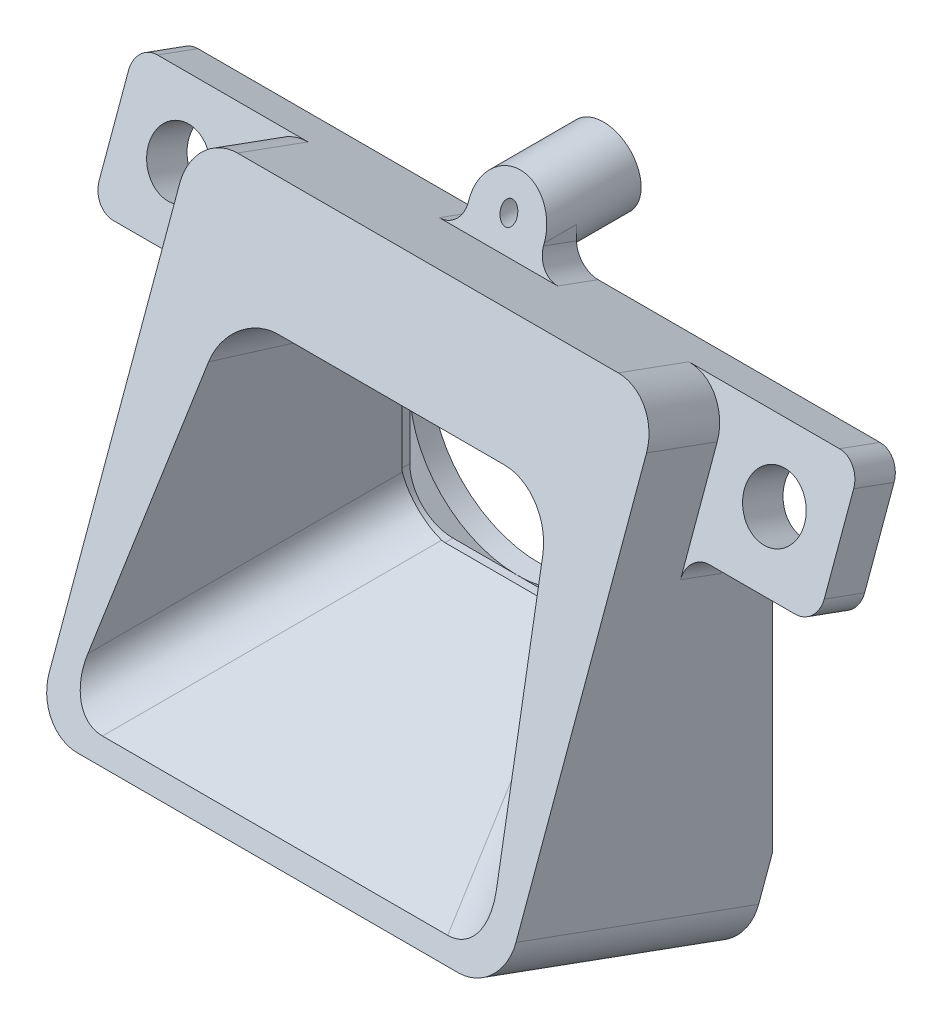
SolidWorks part; units mm, degrees
ref_plane "Front" through (0, 0, 0) normal (0, 0, 1) x (1, 0, 0)
ref_plane "Top" through (0, 0, 0) normal (0, 1, 0) x (1, 0, 0)
ref_plane "Right" through (0, 0, 0) normal (1, 0, 0) x (0, 0, -1)
sketch "Sketch1" plane through (0, 0, 0) normal (0, 0, 1) x (1, 0, 0)
  line L1 (0, 0) -> (40, 0)
  line L2 (0, 0) -> (0, 21.55)
  line L3 (0, 21.55) -> (40, 21.55)
  line L4 (40, 0) -> (40, 21.55)
  dimension "D1" = 40
  dimension "D2" = 21.55
extrude "Boss-Extrude1" add sketch "Sketch1" along normal blind 12.6
sketch "Sketch2" plane through (0, 0, 12.6) normal (0, 0, 1) x (1, 0, 0)
  line L0 (20, 21.55) -> (20, 0) construction
  line L1 (40, 21.55) -> (0, 21.55) construction
  line L2 (0, 0) -> (40, 0) construction
  circle A0 centre (20, 10.775) radius 5
  dimension "D1" = 10
extrude "Cut-Extrude1" cut sketch "Sketch2" against normal through all
sketch "Sketch3" plane through (0, 0, 12.6) normal (0, 0, 1) x (1, 0, 0)
  line L1 (15, 5.775) -> (25, 5.775)
  line L2 (15, 5.775) -> (15, 15.775)
  line L3 (15, 15.775) -> (25, 15.775)
  line L4 (25, 5.775) -> (25, 15.775)
  line L5 (15, 5.775) -> (25, 15.775) construction
  line L6 (15, 15.775) -> (25, 5.775) construction
  circle A0 centre (20, 10.775) radius 5 construction
  point P0 (20, 10.775)
extrude "Cut-Extrude2" cut sketch "Sketch3" against normal offset from surface (11.6 mm away) 1 up to face at (25, 10.775, 0)
chamfer "Chamfer1" distance 5 angle 66 3 edges at (25, 10.775, 12.6) (15, 10.775, 12.6) (20, 5.775, 12.6) first distance on face at (20, 10.775, 12.6)
sketch "Sketch4" plane through (0, 0, 0) normal (-1, 0, 0) x (0, 0, 1)
  line L0 (12.6, 0) -> (5.1642, 20.4296)
  line L1 (5.1642, 20.4296) -> (0, 18.55)
  line L4 (12.6, 0) -> (12.6, 21.55)
  line L5 (0, 21.55) -> (0, 0) construction
  line L6 (0, 18.55) -> (0, 21.55)
  line L7 (0, 21.55) -> (12.6, 21.55)
  dimension "D1" = 20
  dimension "D2" = 3
extrude "Cut-Extrude3" cut sketch "Sketch4" against normal through all
sketch "Sketch5" plane through (0, 0, 0) normal (-1, 0, 0) x (0, 0, 1)
  line L0 (12.6, 0) -> (0, -4.586)
  line L1 (0, -4.586) -> (0, 0)
  line L2 (12.6, 0) -> (0, 0) construction
  line L3 (0, 0) -> (12.6, 0)
  line L4 (0, 18.55) -> (5.1642, 20.4296) construction
  line L5 (0, 18.55) -> (0, 0) construction
extrude "Boss-Extrude2" add sketch "Sketch5" against normal up to surface (40 mm away) up to face at (40, 9.7449, 4.4411)
sketch "Sketch6" plane through (0, 0, -3) normal (0, 0, 1) x (1, 0, 0)
  circle A0 centre (20, 20.275) radius 1.75
  circle A1 centre (20, 1.275) radius 1.75
  dimension "D1" = 3.5
extrude "Boss-Extrude3" add sketch "Sketch6" along normal up to surface (3 mm away) up to face at (20, 6.982, 0)
sketch "Sketch7" plane through (40, 0, 0) normal (1, 0, 0) x (0, 0, -1)
  line L0 (0, -4.586) -> (0, -0.475)
  line L2 (0, -0.475) -> (-1.3213, -4.1051)
  line L3 (-12.6, 0) -> (0, -4.586) construction
  line L4 (-1.3213, -4.1051) -> (0, -4.586)
  line L5 (0, -0.475) -> (0, 3.025) construction
  line L6 (0, -0.475) -> (0, 3.025) construction
extrude "Cut-Extrude4" cut sketch "Sketch7" against normal through all
sketch "Sketch8" plane through (0, 4.0496, 11.1261) normal (0, 0.342, 0.9397) x (1, 0, 0)
  line L0 (0, -4.3095) -> (40, -4.3095) construction
  line L1 (0, 17.4313) -> (9.1499, 17.4313)
  line L2 (0, 17.4313) -> (0, -4.3095)
  line L3 (0, -4.3095) -> (9.1499, -4.3095)
  line L4 (9.1499, 17.4313) -> (9.1499, -4.3095)
  line L5 (20, -4.3095) -> (20, 17.4313) construction
  line L6 (40, 17.4313) -> (0, 17.4313) construction
  line L7 (40, -4.3095) -> (30.8501, -4.3095)
  line L8 (30.8501, 17.4313) -> (30.8501, -4.3095)
  line L9 (40, 17.4313) -> (30.8501, 17.4313)
  line L10 (40, 17.4313) -> (40, -4.3095)
  dimension "D1" = 1
extrude "Cut-Extrude5" cut sketch "Sketch8" against normal through all
sketch "Sketch11" plane through (9.1499, 0, 0) normal (-1, 0, 0) x (0, 0, 1)
  line L0 (0, 18.55) -> (1.8794, 19.234)
  line L1 (0, 18.55) -> (2.0521, 12.9118)
  line L2 (1.8794, 19.234) -> (3.9315, 13.5959)
  line L3 (2.0521, 12.9118) -> (3.9315, 13.5959)
  line L4 (0, 18.55) -> (5.1642, 20.4296) construction
  dimension "D1" = 2
  dimension "D2" = 6
extrude "Boss-Extrude4" add sketch "Sketch11" along normal blind 6
ref_plane "Plane1" through (20, 0, 0) normal (-1, 0, 0) x (0, 0, 1)
sketch "Sketch12" plane through (0, 2.854, 7.8412) normal (0, 0.342, 0.9397) x (1, 0, 0)
  line L0 (3.1499, 11.4313) -> (9.1499, 17.4313) construction
  circle A0 centre (6.1499, 14.4313) radius 1.4
  dimension "D1" = 2.8
extrude "Cut-Extrude6" cut sketch "Sketch12" against normal through all
mirror "Mirror1" about plane through (20, 0, 0) normal (-1, 0, 0) of "Cut-Extrude6", "Boss-Extrude4"
sketch "Sketch14" plane through (0, 2.854, 7.8412) normal (0, 0.342, 0.9397) x (1, 0, 0)
  line L0 (19.7053, 17.4313) -> (9.1499, 17.4313) construction
  line L1 (18.25, 17.4313) -> (21.75, 17.4313)
  line L2 (18.25, 17.4313) -> (18.25, 20.6967)
  line L3 (18.25, 20.6967) -> (21.75, 20.6967)
  line L4 (21.75, 17.4313) -> (21.75, 20.6967)
  ellipse E0 centre (20, 20.0783) end of major axis (18.25, 20.0783) minor radius 1.6445 construction
  ellipse E1 centre (20, 19.0523) end of major axis (21.75, 19.0523) minor radius 1.6445 (20.2947, 17.4313) -> (19.7053, 17.4313) ccw construction
extrude "Boss-Extrude5" add sketch "Sketch14" against normal up to surface (2 mm away) up to face at (20, 20.2875, 0)
sketch "Sketch15" plane through (0, 0, 0) normal (0, 0, -1) x (-1, 0, 0)
  line L2 (-20, 22.025) -> (-21.75, 22.025)
  line L3 (-21.75, 22.025) -> (-21.75, 20.275)
  line L4 (-20, 22.025) -> (-21.75, 22.025)
  line L5 (-21.75, 22.025) -> (-21.75, 20.275)
  arc A1 (-20, 22.025) -> (-21.75, 20.275) centre (-20, 20.275) ccw
  arc A2 (-20, 22.025) -> (-21.75, 20.275) centre (-20, 20.275) ccw
  dimension "D1" = 0
extrude "Cut-Extrude7" cut sketch "Sketch15" against normal up to surface (0.8636 mm away) up to face at (20, 20.7683, 1.321)
sketch "Sketch16" plane through (0, 0, 0) normal (0, 0, -1) x (-1, 0, 0)
  line L2 (-18.25, 20.275) -> (-18.25, 22.025)
  line L3 (-18.25, 22.025) -> (-20, 22.025)
  line L4 (-18.25, 20.275) -> (-18.25, 22.025)
  line L5 (-18.25, 22.025) -> (-20, 22.025)
  arc A1 (-18.25, 20.275) -> (-20, 22.025) centre (-20, 20.275) ccw
  arc A2 (-18.25, 20.275) -> (-20, 22.025) centre (-20, 20.275) ccw
  dimension "D1" = 0
extrude "Cut-Extrude8" cut sketch "Sketch16" against normal up to surface (1.5005 mm away) up to face at (20.5518, 21.1087, 1.1971)
hole_wizard "M2 Tapped Hole1" positions "3DSketch1" profile "Sketch17" tap size "M2" standard "ISO"
sketch3d "3DSketch1"
  line L0 (20, 20.275, 0) -> (20, 20.275, -3) construction
  line L1 (20, 1.275, 0) -> (20, 1.275, -3) construction
  point P0 (20, 20.275, -3)
  point P4 (20, 1.275, -3)
sketch "Sketch17" plane through (20, 20.275, -3) normal (1, 0, 0) x (0, 1, 0)
  line L0 (0, 0) -> (0, 4.6807)
  line L1 (0, 4.6807) -> (0.8, 4.2)
  line L2 (0.8, 4.2) -> (0.8, 0)
  line L5 (0.8, 0) -> (0, 0)
  line L10 (0, 4.6807) -> (-0.8, 4.2) construction
  line L11 (0, -6.35) -> (0, 107.95) construction
  dimension "Tap Drill Dia." = 1.6
  dimension "Tap Drill Depth" = 4.2
  dimension "Drill Angle" = 118
cosmetic thread "Hole Thread1" parameters "D1"=3, "D2"=2
cosmetic thread "Hole Thread2" parameters "D1"=3, "D2"=2
fillet "Fillet1" radius 1 8 edges at (30.8501, 13.2539, 2.9918) (36.8501, 13.2539, 2.9918) (36.8501, 18.892, 0.9397) (21.75, 18.892, 0.9397) (18.25, 18.892, 0.9397) (3.1499, 18.892, 0.9397) (9.1499, 13.2539, 2.9918) (3.1499, 13.2539, 2.9918)
fillet "Fillet2" radius 2 4 edges at (30.8501, 19.8318, 3.5218) (9.1499, 19.8318, 3.5218) (30.8501, -2.0526, 6.9606) (9.1499, -2.0526, 6.9606)
fillet "Fillet4" radius 2 8 edges at (15, 15.775, 1.1849) (25, 15.775, 1.1849) (25, 5.775, 1.1849) (15, 5.775, 1.1849) (26.2218, 15.775, 4.1141) (13.7782, 15.775, 4.1141) (27.4251, 3.3499, 6.8166) (12.5749, 3.3499, 6.8166)
